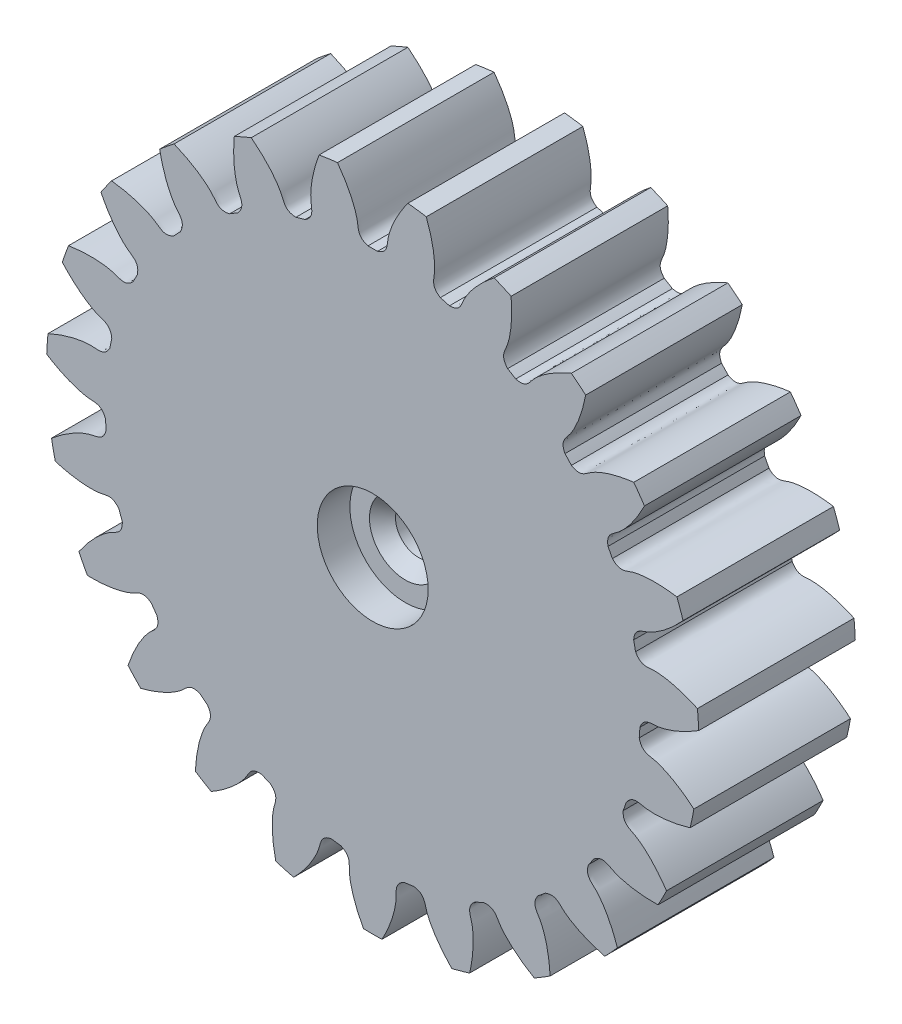
SolidWorks part; units mm, degrees
ref_plane "前视基准面" through (0, 0, 0) normal (0, 0, 1) x (1, 0, 0)
ref_plane "上视基准面" through (0, 0, 0) normal (0, 1, 0) x (1, 0, 0)
ref_plane "右视基准面" through (0, 0, 0) normal (1, 0, 0) x (0, 0, -1)
sketch "草图1" plane through (0, 0, 0) normal (0, 0, 1) x (1, 0, 0)
  circle A0 centre (0, 0) radius 25
extrude "凸台-拉伸1" add sketch "草图1" along normal blind 12
ref_axis "基准轴1" through (0, 0, -0.6) along (0, 0, 1)
sketch "草图2" plane through (0, 0, 0) normal (0, 0, 1) x (1, 0, 0)
  line L0 (0, 0) -> (0, 25) construction
  circle A0 centre (0, 0) radius 25 construction
  arc A1 (0.3628, 20.4968) -> (-0.3628, 20.4968) centre (0, 0) ccw
  arc A2 (6.3634, 28.3724) -> (-6.3634, 28.3724) centre (0, 0) ccw
  spline S0 degree 3 poles (0.3628, 20.4968) (1.1555, 20.7335) (1.0875, 21.2677) (1.1859, 21.7944) (1.199, 21.8578) (1.2153, 21.9295) (1.2352, 22.0092) (1.2588, 22.0968) (1.2867, 22.1923) (1.319, 22.2954) (1.3562, 22.4061) (1.3984, 22.5241) (1.4461, 22.6493) (1.4995, 22.7816) (1.5589, 22.9207) (1.6247, 23.0665) (1.6971, 23.2188) (1.7763, 23.3773) (1.8628, 23.5419) (1.9567, 23.7122) (2.0583, 23.8882) (2.1678, 24.0695) (2.2856, 24.2558) (2.4119, 24.447) (2.5468, 24.6427) (2.6907, 24.8428) (2.8438, 25.0468) (3.0062, 25.2545) (3.1782, 25.4657) (3.36, 25.6799) (3.5517, 25.897) (3.7537, 26.1165) (3.9659, 26.3382) (4.1886, 26.5618) (4.422, 26.7868) (4.6662, 27.013) (4.9213, 27.24) (5.1875, 27.4675) (5.4648, 27.6952) (5.8542, 28.0019) (6.1566, 28.2256) (6.3634, 28.3724) knots 0 0 0 0 0.147387 0.15296 0.159389 0.166677 0.174821 0.183823 0.193683 0.204399 0.215973 0.228404 0.241693 0.255839 0.270842 0.286703 0.303421 0.320996 0.339428 0.358718 0.378866 0.39987 0.421732 0.444451 0.468028 0.492462 0.517753 0.543901 0.570907 0.59877 0.627491 0.657069 0.687504 0.718796 0.750946 0.783953 0.817818 0.85254 0.888119 0.924555 1 1 1 1
  spline S1 degree 3 poles (-0.3628, 20.4968) (-1.1555, 20.7335) (-1.0875, 21.2677) (-1.1859, 21.7944) (-1.199, 21.8578) (-1.2153, 21.9295) (-1.2352, 22.0092) (-1.2588, 22.0968) (-1.2867, 22.1923) (-1.319, 22.2954) (-1.3562, 22.4061) (-1.3984, 22.5241) (-1.4461, 22.6493) (-1.4995, 22.7816) (-1.5589, 22.9207) (-1.6247, 23.0665) (-1.6971, 23.2188) (-1.7763, 23.3773) (-1.8628, 23.5419) (-1.9567, 23.7122) (-2.0583, 23.8882) (-2.1678, 24.0695) (-2.2856, 24.2558) (-2.4119, 24.447) (-2.5468, 24.6427) (-2.6907, 24.8428) (-2.8438, 25.0468) (-3.0062, 25.2545) (-3.1782, 25.4657) (-3.36, 25.6799) (-3.5517, 25.897) (-3.7537, 26.1165) (-3.9659, 26.3382) (-4.1886, 26.5618) (-4.422, 26.7868) (-4.6662, 27.013) (-4.9213, 27.24) (-5.1875, 27.4675) (-5.4648, 27.6952) (-5.8542, 28.0019) (-6.1566, 28.2256) (-6.3634, 28.3724) knots 0 0 0 0 0.147387 0.15296 0.159389 0.166677 0.174821 0.183823 0.193683 0.204399 0.215973 0.228404 0.241693 0.255839 0.270842 0.286703 0.303421 0.320996 0.339428 0.358718 0.378866 0.39987 0.421732 0.444451 0.468028 0.492462 0.517753 0.543901 0.570907 0.59877 0.627491 0.657069 0.687504 0.718796 0.750946 0.783953 0.817818 0.85254 0.888119 0.924555 1 1 1 1
extrude "切除-拉伸1" cut sketch "草图2" along normal through all
pattern_circular "阵列(圆周)1" count 23 every 15.652 about axis through (0, 0, -0.6) along (0, 0, 1) of "切除-拉伸1"
sketch "草图3" plane through (0, 0, 0) normal (0, 0, 1) x (1, 0, 0)
  circle A0 centre (0, 0) radius 23 construction
  dimension "Dn" = 46
sketch "草图4" plane through (0, 0, 0) normal (0, 0, -1) x (-1, 0, 0)
  circle A0 centre (0, 0) radius 1.75
  dimension "D1" = 3.5
extrude "切除-拉伸2" cut sketch "草图4" against normal through all
sketch "草图5" plane through (0, 0, 0) normal (0, 0, -1) x (-1, 0, 0)
  line L0 (0, 19.9605) -> (0, -21.6983) construction
  line L1 (-19.7914, 0) -> (19.4454, 0) construction
  line L3 (10.623, 10.623) -> (-10.8701, -10.8701) construction
  line L4 (-4.9497, 4.9497) -> (-4.9497, 7.9497)
  line L5 (-4.9497, 7.9497) -> (-2.5, 20)
  line L6 (-2.5, 20) -> (2.5, 20)
  line L8 (-4.9497, 4.9497) -> (-7.9497, 4.9497)
  line L9 (-7.9497, 4.9497) -> (-20, 2.5)
  line L10 (-20, 2.5) -> (-20, -2.5)
  line L11 (20, 2.5) -> (20, -2.5)
  line L12 (7.9497, 4.9497) -> (20, 2.5)
  line L13 (4.9497, 4.9497) -> (7.9497, 4.9497)
  line L14 (4.9497, 4.9497) -> (4.9497, 7.9497)
  line L15 (4.9497, 7.9497) -> (2.5, 20)
  line L18 (7.9497, -4.9497) -> (20, -2.5)
  line L19 (4.9497, -4.9497) -> (7.9497, -4.9497)
  line L20 (4.9497, -4.9497) -> (4.9497, -7.9497)
  line L21 (4.9497, -7.9497) -> (2.5, -20)
  line L22 (-2.5, -20) -> (2.5, -20)
  line L23 (-4.9497, -7.9497) -> (-2.5, -20)
  line L24 (-4.9497, -4.9497) -> (-4.9497, -7.9497)
  line L25 (-4.9497, -4.9497) -> (-7.9497, -4.9497)
  line L26 (-7.9497, -4.9497) -> (-20, -2.5)
  circle A1 centre (0, 0) radius 7 construction
  point P0 (-4.9497, 4.9497)
  point P11 (4.9497, 4.9497)
  point P12 (4.9497, -4.9497)
  point P13 (-4.9497, -4.9497)
  point P27 (0, 20)
  point P28 (20, 0)
  point P37 (-20, 0)
  dimension "D1" = 14
  dimension "D2" = 45
  dimension "D3" = 3
  dimension "D4" = 2.5
  dimension "D5" = 20
extrude "切除-拉伸4" cut sketch "草图5" against normal blind 2.5
sketch "草图7" plane through (0, 0, 12) normal (0, 0, 1) x (1, 0, 0)
  circle A0 centre (0, 0) radius 4.25
  dimension "D1" = 8.5
extrude "切除-拉伸5" cut sketch "草图7" against normal blind 2.5
sketch "草图8" plane through (0, 0, 2.5) normal (0, 0, -1) x (-1, 0, 0)
  circle A0 centre (0, 0) radius 5
  dimension "D1" = 10
extrude "切除-拉伸6" cut sketch "草图8" against normal blind 3
fillet "圆角2" radius 1 5 edges at (-4.9497, -4.9497, 1.25) (4.9497, -4.9497, 1.25) (-4.9497, 4.9497, 1.25) (4.9497, 4.9497, 1.25) (-5, 0, 2.5)
fillet "圆角4" radius 2 8 edges at (-20, 2.5, 1.25) (-20, -2.5, 1.25) (-2.5, -20, 1.25) (2.5, -20, 1.25) (20, -2.5, 1.25) (20, 2.5, 1.25) (-2.5, 20, 1.25) (2.5, 20, 1.25)
chamfer "倒角2" distance 1 angle 45 1 edges at (1.75, 0, 9.5)
